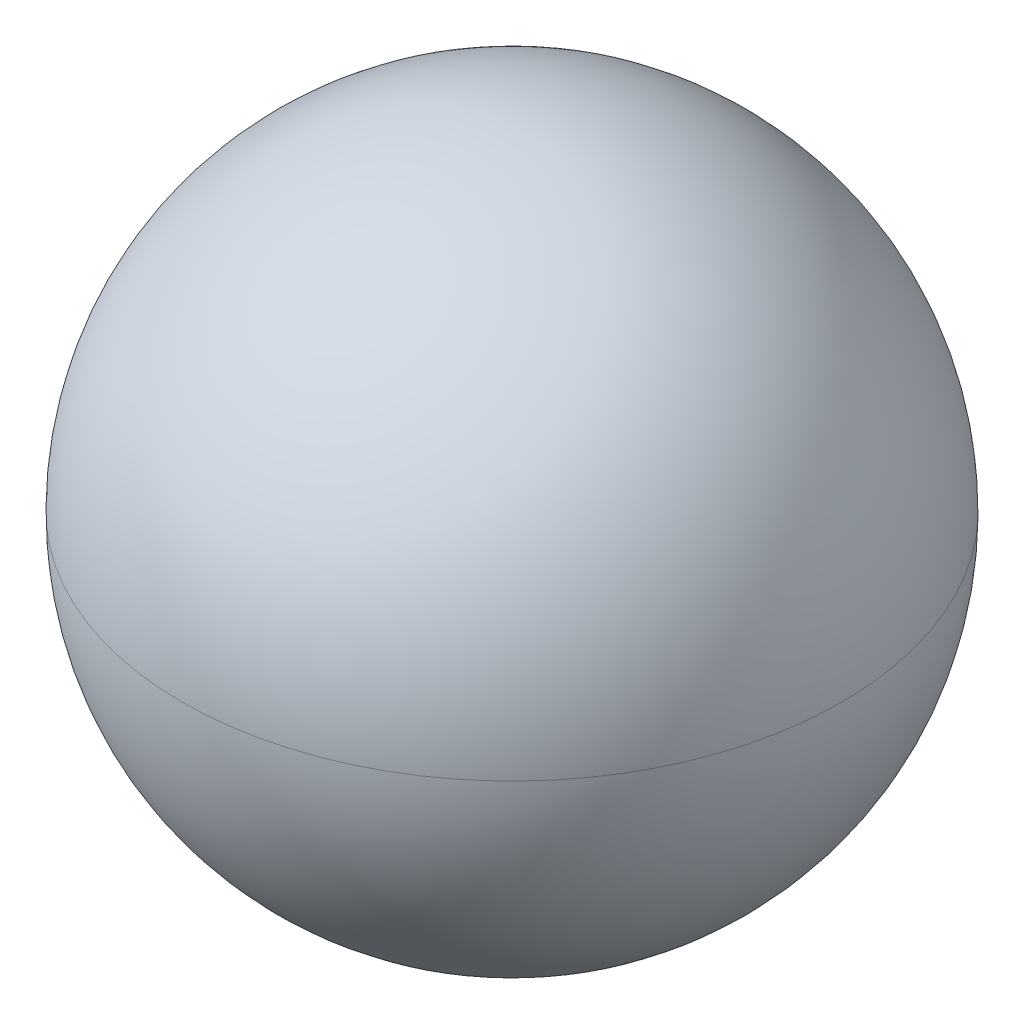
SolidWorks part; units mm, degrees
ref_plane "Front Plane" through (0, 0, 0) normal (0, 0, 1) x (1, 0, 0)
ref_plane "Top Plane" through (0, 0, 0) normal (0, 1, 0) x (1, 0, 0)
ref_plane "Right Plane" through (0, 0, 0) normal (1, 0, 0) x (0, 0, -1)
sketch "Sketch1" plane through (0, 0, 0) normal (0, 1, 0) x (1, 0, 0)
  circle A0 centre (0, 0) radius 3
  dimension "D1" = 6
extrude "Boss-Extrude1" add sketch "Sketch1" along normal blind 6 contours A0
sketch "Sketch2" plane through (0, 0, 0) normal (0, 0, 1) x (1, 0, 0)
  line L0 (0, 6) -> (0, 0) construction
  line L1 (3, 6) -> (-3, 6) construction
  line L2 (3, 3) -> (-3, 3) construction
  line L3 (3, 0) -> (3, 6) construction
  line L4 (-3, 6) -> (-3, 0) construction
  line L8 (0, 6) -> (0, 0)
  arc A0 (0, 6) -> (3, 3) centre (0, 3) cw
  arc A1 (0, 0) -> (3, 3) centre (0, 3) ccw
  dimension "D1" = 3
ref_axis "Axis1" through (0, 6, 0) along (0, -1, 0)
fillet "Fillet1" radius 3 2 edges at (0, 6, 3) (0, 0, 3)
sketch "Sketch3" plane through (0, 0, 0) normal (0, 1, 0) x (1, 0, 0)
  line L0 (0, -3) -> (0, 3) construction
  line L2 (-3, 0) -> (3, 0) construction
  line L3 (0, 0) -> (3, 0) construction
  line L4 (3, 0) -> (-3, 0) construction
  circle A0 centre (0, 0) radius 3 construction
  point P0 (0, 3)
  point P4 (0, 0)
  point P12 (0, 0)
